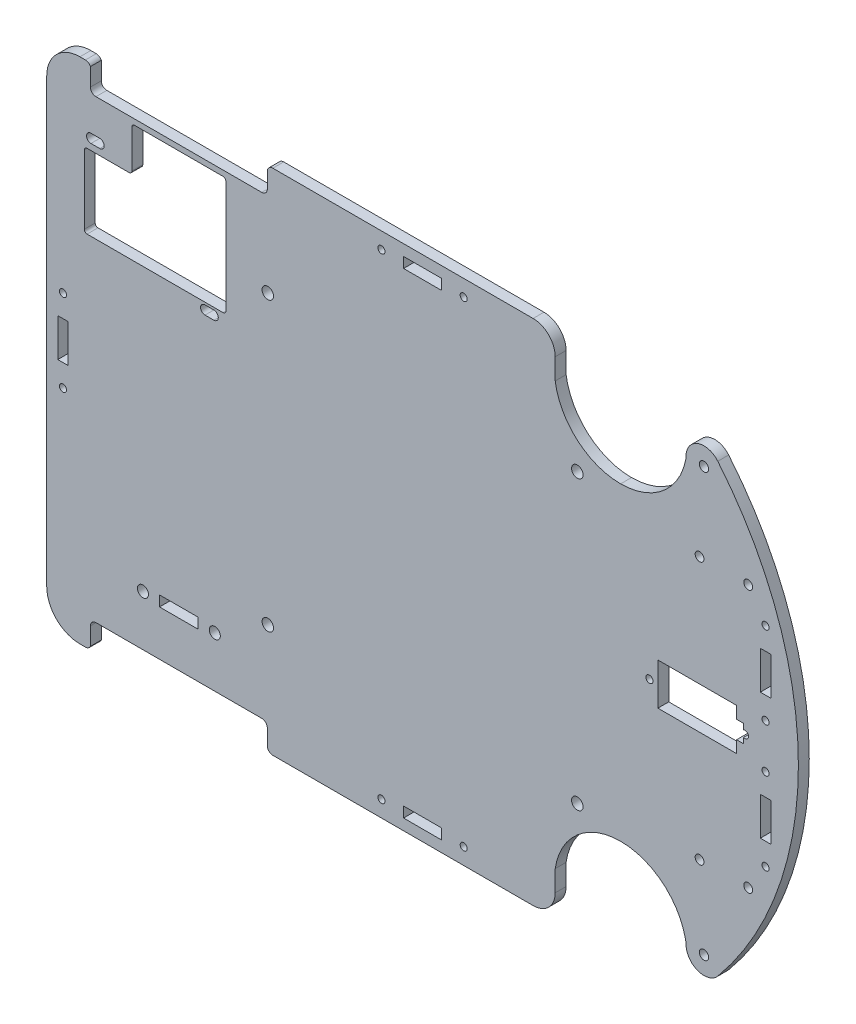
SolidWorks part; units mm, degrees
ref_plane "Alzado" through (0, 0, 0) normal (0, 0, 1) x (1, 0, 0)
ref_plane "Planta" through (0, 0, 0) normal (0, 1, 0) x (1, 0, 0)
ref_plane "Vista lateral" through (0, 0, 0) normal (1, 0, 0) x (0, 0, -1)
sketch "Croquis1" plane through (0, 0, 0) normal (0, 0, 1) x (1, 0, 0)
  line L1 (-107.95, -73.025) -> (107.95, -73.025)
  line L2 (-107.95, -73.025) -> (-107.95, 73.025)
  line L3 (-107.95, 73.025) -> (107.95, 73.025)
  line L4 (107.95, -73.025) -> (107.95, 73.025)
  line L5 (-107.95, -73.025) -> (107.95, 73.025) construction
  line L6 (-107.95, 73.025) -> (107.95, -73.025) construction
  point P0 (0, 0)
  dimension "D1" = 146.05
  dimension "D2" = 215.9
extrude "Saliente-Extruir1" add sketch "Croquis1" along normal blind 3.1242
sketch "Croquis2" plane through (0, 0, 3.1242) normal (0, 0, 1) x (1, 0, 0)
  line L0 (-107.95, -73.025) -> (107.95, -73.025) construction
  line L1 (107.95, 73.025) -> (43.634, 73.025)
  line L2 (107.95, 73.025) -> (107.95, -73.025)
  line L3 (107.95, -73.025) -> (43.634, -73.025)
  line L4 (43.634, 73.025) -> (43.634, -73.025)
  line L5 (0, 0) -> (107.95, 0) construction
  line L6 (71.3851, 73.025) -> (80.1989, 73.025)
  line L7 (71.3851, 73.025) -> (71.3851, 55.6514)
  line L8 (71.3851, 55.6514) -> (80.1989, 55.6514)
  line L9 (80.1989, 73.025) -> (80.1989, 55.6514)
  line L10 (80.1989, -73.025) -> (80.1989, -55.6514)
  line L11 (71.3851, -55.6514) -> (80.1989, -55.6514)
  line L12 (71.3851, -73.025) -> (71.3851, -55.6514)
  line L13 (71.3851, -73.025) -> (80.1989, -73.025)
  circle A0 centre (80.8339, 60.7314) radius 2.921
  circle A1 centre (80.8339, 60.7314) radius 1.3335
  circle A2 centre (80.8339, -60.7314) radius 1.3335
  circle A3 centre (80.8339, -60.7314) radius 2.921
  point P11 (75.792, 73.025)
  point P12 (75.792, 55.6514)
  point P13 (80.8339, 57.8104)
  point P14 (83.7549, 60.7314)
  point P28 (83.7549, -60.7314)
  point P29 (80.8339, -57.8104)
  point P30 (75.792, -55.6514)
  point P31 (75.792, -73.025)
  point P32 (80.8339, -59.3979)
  point P33 (80.8339, 59.3979)
  point P34 (80.8339, -62.0649)
  point P35 (80.8339, 62.0649)
  dimension "D3" = 5.842
  dimension "D4" = 1.5875
  dimension "D1" = 43.634
  dimension "D2" = 8.8138
  dimension "D5" = 3.556
  dimension "D6" = 17.3736
  dimension "D7" = 118.7958
  dimension "D8" = 118.7958
  dimension "D9" = 124.1298
extrude "Cortar-Extruir1" cut sketch "Croquis2" against normal through all contours L9 A1 | L9 A1 | A2 region at (81.0771, 60.7314, 3.1242) region at (79.9121, 60.7314, 3.1242)
sketch "Croquis9" plane through (0, 0, 3.1242) normal (0, 0, 1) x (1, 0, 0)
  line L0 (68.1339, 37.6809) -> (93.5339, 37.6809) construction
  line L1 (0, 0) -> (107.95, 0) construction
  line L2 (107.95, -73.025) -> (107.95, 73.025) construction
  line L3 (68.1339, -37.6809) -> (93.5339, -37.6809) construction
  circle A0 centre (68.1339, 37.6809) radius 1.27
  circle A1 centre (93.5339, 37.6809) radius 1.27
  circle A2 centre (93.5339, 37.6809) radius 2.794
  circle A3 centre (80.8339, 60.7314) radius 1.3335 construction
  circle A4 centre (80.8339, 60.7314) radius 1.3335
  circle A5 centre (93.5339, -37.6809) radius 1.27
  circle A6 centre (68.1339, -37.6809) radius 1.27
  circle A7 centre (80.8339, 37.6809) radius 1.27
  circle A8 centre (80.8339, -37.6809) radius 1.27
  circle A9 centre (79.5639, 37.6809) radius 1.27
  circle A10 centre (79.5639, -37.6809) radius 1.27
  point P4 (80.8339, 62.0649)
  point P5 (93.5339, 34.8869)
  point P9 (80.8339, 37.6809)
  point P22 (93.5339, -34.8869)
  point P23 (69.4039, 37.6809)
  point P24 (92.2639, 37.6809)
  dimension "D1" = 12.7
  dimension "D2" = 2.54
  dimension "D3" = 27.178
  dimension "D4" = 5.588
  dimension "D5" = 23.0505
  dimension "D6" = 2.667
extrude "Cortar-Extruir6" cut sketch "Croquis9" against normal through all contours A9 | A1 | A10 | A5
sketch "Croquis3" plane through (0, 0, 3.1242) normal (0, 0, 1) x (1, 0, 0)
  line L0 (107.95, -73.025) -> (107.95, 73.025) construction
  line L1 (107.95, 73.025) -> (-107.95, 73.025) construction
  line L2 (0, 0) -> (107.95, 0) construction
  line L3 (38.1, 73.025) -> (75.6745, 73.025)
  line L4 (38.1, 73.025) -> (38.1, 44.45)
  line L5 (38.1, 44.45) -> (75.6745, 44.45)
  line L6 (75.6745, 73.025) -> (75.6745, 44.45)
  line L7 (75.6745, -73.025) -> (75.6745, -44.45)
  line L8 (38.1, -44.45) -> (75.6745, -44.45)
  line L9 (38.1, -73.025) -> (38.1, -44.45)
  line L10 (38.1, -73.025) -> (75.6745, -73.025)
  line L11 (-107.95, -73.025) -> (107.95, -73.025) construction
  line L12 (-98.425, 73.025) -> (0, 73.025)
  line L13 (-107.95, 63.5) -> (-107.95, -63.5)
  line L14 (-98.425, -73.025) -> (0, -73.025)
  line L15 (0, 73.025) -> (0, -73.025)
  circle A0 centre (80.8339, 60.7314) radius 5.1594
  arc A1 (84.8004, 64.0308) -> (84.8004, -64.0308) centre (7.8219, 0) cw
  arc A2 (75.6745, 60.7314) -> (75.5727, 59.7195) centre (70.5945, 60.7314) cw
  arc A3 (31.75, 73.025) -> (38.1, 66.675) centre (31.75, 66.675) cw
  arc A4 (38.0482, 65.8655) -> (56.8873, 44.45) centre (56.8873, 63.4441) ccw
  arc A5 (38.0482, -65.8655) -> (56.8873, -44.45) centre (56.8873, -63.4441) cw
  arc A6 (31.75, -73.025) -> (38.1, -66.675) centre (31.75, -66.675) ccw
  arc A7 (75.5727, -59.7195) -> (56.8873, -44.45) centre (56.8873, -63.5176) ccw
  circle A8 centre (80.8339, -60.7314) radius 5.1594
  arc A9 (-107.95, -63.5) -> (-98.425, -73.025) centre (-98.425, -63.5) ccw
  arc A10 (-98.425, 73.025) -> (-107.95, 63.5) centre (-98.425, 63.5) ccw
  arc A11 (75.5727, 59.7195) -> (56.8873, 44.45) centre (56.8873, 63.5176) cw
  arc A12 (75.6745, -60.7314) -> (75.5727, -59.7195) centre (70.5945, -60.7314) ccw
  point P48 (-107.95, 73.025)
  line M6 (107.95, -73.025) -> (107.95, 73.025)
  line M7 (107.95, 73.025) -> (-107.95, 73.025)
  line M8 (-107.95, 73.025) -> (-107.95, -73.025)
  line M9 (-107.95, -73.025) -> (107.95, -73.025)
  dimension "D1" = 28.575
  dimension "D3" = 6.35
  dimension "D4" = 9.525
  dimension "D5" = 10.3187
  dimension "D6" = 5.08
  dimension "D2" = 38.1
extrude "Cortar-Extruir2" cut sketch "Croquis3" against normal through all contours A3 A4 L4 M7 | A11 A2 L6 L4 A4 M7 | A0 A1 L6 M6 M7 | A1 A8 L7 M9 M6 | L7 A12 A7 A5 L9 M9 | A6 L9 A5 M9 | A10 M7 M8 | A9 M8 M9 region at (56.8973, 60.3698, 3.1242) region at (36.6816, 71.6066, 3.1242) region at (97.7834, 56.0016, 3.1242) region at (97.7834, -56.0016, 3.1242) region at (-105.8224, 70.8974, 3.1242) region at (-105.8224, -70.8974, 3.1242) region at (36.6816, -71.6066, 3.1242) region at (56.8973, -60.3698, 3.1242)
sketch "Croquis5" plane through (0, 0, 3.1242) normal (0, 0, 1) x (1, 0, 0)
  line L0 (-98.425, -73.025) -> (31.75, -73.025) construction
  line L1 (-17.0815, -19.2786) -> (33.3375, -19.2786)
  line L2 (-17.0815, -19.2786) -> (-17.0815, -69.85)
  line L3 (-17.0815, -69.85) -> (33.3375, -69.85)
  line L4 (33.3375, -19.2786) -> (33.3375, -69.85)
  line L5 (-17.0815, -44.5643) -> (33.3375, -44.5643) construction
  line L6 (38.1, -66.675) -> (38.1, -60.6489) construction
  line L7 (33.3375, -69.85) -> (25.9715, -69.85)
  line L8 (33.3375, -69.85) -> (33.3375, -19.2786)
  line L9 (33.3375, -19.2786) -> (25.9715, -19.2786)
  line L10 (25.9715, -69.85) -> (25.9715, -19.2786)
  line L11 (-17.0815, -19.2786) -> (-6.9215, -19.2786)
  line L12 (-17.0815, -19.2786) -> (-17.0815, -69.85)
  line L13 (-17.0815, -69.85) -> (-6.9215, -69.85)
  line L14 (-6.9215, -19.2786) -> (-6.9215, -69.85)
  line L15 (25.9715, -33.2486) -> (33.3375, -33.2486)
  line L16 (25.9715, -33.2486) -> (25.9715, -55.88)
  line L17 (25.9715, -55.88) -> (33.3375, -55.88)
  line L18 (33.3375, -33.2486) -> (33.3375, -55.88)
  line L19 (-6.9215, -29.0576) -> (-17.0815, -29.0576)
  line L20 (-6.9215, -29.0576) -> (-6.9215, -60.071)
  line L21 (-6.9215, -60.071) -> (-17.0815, -60.071)
  line L22 (-17.0815, -29.0576) -> (-17.0815, -60.071)
  circle A0 centre (29.7815, -24.7396) radius 1.651
  circle A1 centre (-10.3505, -24.6126) radius 1.651
  circle A2 centre (29.7815, -64.389) radius 1.651
  circle A3 centre (-10.3505, -64.516) radius 1.651
  arc A4 (31.75, -55.88) -> (33.3375, -54.2925) centre (31.75, -54.2925) ccw
  arc A5 (29.6545, -55.88) -> (25.9715, -59.563) centre (29.6545, -59.563) ccw
  arc A6 (-12.0015, -60.071) -> (-17.0815, -54.991) centre (-12.0015, -54.991) cw
  arc A7 (-10.0965, -60.071) -> (-6.9215, -63.246) centre (-10.0965, -63.246) cw
  arc A8 (31.75, -33.2486) -> (33.3375, -34.8361) centre (31.75, -34.8361) cw
  arc A9 (29.6545, -33.2486) -> (25.9715, -29.5656) centre (29.6545, -29.5656) cw
  arc A10 (-12.0015, -29.0576) -> (-17.0815, -34.1376) centre (-12.0015, -34.1376) ccw
  arc A11 (-10.0965, -29.0576) -> (-6.9215, -25.8826) centre (-10.0965, -25.8826) ccw
  arc A12 (-6.9215, -20.0724) -> (-6.1278, -19.2786) centre (-6.1278, -20.0724) cw
  arc A13 (25.1777, -19.2786) -> (25.9715, -20.0724) centre (25.1777, -20.0724) cw
  arc A14 (25.1777, -69.85) -> (25.9715, -69.0563) centre (25.1777, -69.0563) ccw
  arc A15 (-6.9215, -69.0563) -> (-6.1278, -69.85) centre (-6.1278, -69.0563) ccw
  point P4 (31.4325, -24.7396)
  point P5 (29.7815, -23.0886)
  point P6 (-10.3505, -22.9616)
  point P14 (-12.0015, -24.6126)
  dimension "D5" = 3.302
  dimension "D16" = 1.5875
  dimension "D17" = 3.175
  dimension "D18" = 0.7937
  dimension "D1" = 50.5714
  dimension "D2" = 50.419
  dimension "D3" = 3.81
  dimension "D4" = 1.905
  dimension "D6" = 3.175
  dimension "D7" = 4.7625
  dimension "D8" = 5.08
  dimension "D9" = 3.683
  dimension "D10" = 7.366
  dimension "D11" = 10.16
  dimension "D12" = 13.97
  dimension "D13" = 13.97
  dimension "D14" = 9.779
  dimension "D15" = 9.779
extrude "Driver" [suppressed] cut sketch "Croquis5" against normal through all contours L22 L5 L14 L19 A10 | L5 L12 A6 L21 L20 | L14 L5 L16 L10 L1 | L16 L5 L18 A8 L15 | L5 L10 L17 A4 L8 | L5 L20 L14 L3 L10 | A5 L17 L10 | L21 A7 L14 | A11 L19 L14 | L15 A9 L10 | A1 | A3 | A2 | A0
sketch "Croquis6" [suppressed] plane through (0, 0, 3.1242) normal (0, 0, 1) x (1, 0, 0)
  line L0 (-33.45, 19.8814) -> (22.55, 19.8814)
  line L1 (-29.95, 48.8814) -> (19.05, 48.8814)
  line L2 (-29.95, 48.8814) -> (-29.95, -9.1186)
  line L3 (-29.95, -9.1186) -> (19.05, -9.1186)
  line L4 (19.05, 48.8814) -> (19.05, -9.1186)
  line L5 (-6.1278, -19.2786) -> (25.1777, -19.2786) construction
  line L6 (-5.45, -9.1186) -> (-5.45, 74.7014)
  line L7 (38.1, 66.675) -> (38.1, 60.6489) construction
  circle A0 centre (-29.95, 48.8814) radius 1.651
  circle A1 centre (19.05, 48.8814) radius 1.651
  circle A2 centre (19.05, -9.1186) radius 1.651
  circle A3 centre (-29.95, -9.1186) radius 1.651
  point P13 (-5.45, 19.8814)
  point P14 (19.05, 19.8814)
  point P16 (-5.45, 48.8814)
  point P19 (38.1, 63.662)
  dimension "D1" = 3.302
  dimension "D2" = 58
  dimension "D3" = 49
  dimension "D4" = 56
  dimension "D5" = 19.05
  dimension "D6" = 10.16
  dimension "D7" = 83.82
extrude "RasPi" [suppressed] cut sketch "Croquis6" against normal through all contours A3 | A2 | A1 | A0
sketch "Croquis8" plane through (0, 0, 3.1242) normal (0, 0, 1) x (1, 0, 0)
  line L0 (-93.98, 54.3306) -> (-61.214, 28.0162)
  line L1 (-62.484, 28.0162) -> (-59.944, 28.0162) construction
  line L7 (-62.484, 29.2862) -> (-59.944, 29.2862)
  line L11 (-62.484, 26.7462) -> (-59.944, 26.7462)
  line L13 (-77.597, 66.3702) -> (-77.597, -66.3702) construction
  line L14 (-95.25, 54.3306) -> (-92.71, 54.3306) construction
  line L15 (-95.25, 55.6006) -> (-92.71, 55.6006)
  line L16 (-95.25, 53.0606) -> (-92.71, 53.0606)
  circle A0 centre (-93.98, 54.3306) radius 1.27
  circle A1 centre (-61.214, 28.0162) radius 1.27
  arc A2 (-62.484, 29.2862) -> (-62.484, 26.7462) centre (-62.484, 28.0162) ccw
  arc A3 (-59.944, 26.7462) -> (-59.944, 29.2862) centre (-59.944, 28.0162) ccw
  arc A4 (-95.25, 55.6006) -> (-95.25, 53.0606) centre (-95.25, 54.3306) ccw
  arc A5 (-92.71, 53.0606) -> (-92.71, 55.6006) centre (-92.71, 54.3306) ccw
  point P8 (-61.214, 26.7462)
  point P9 (-93.98, 53.0606)
  point P10 (-95.25, 54.3306)
  point P12 (-59.944, 28.0162)
  point P14 (-77.597, 0)
  point P16 (-61.214, 28.0162)
  point P22 (-93.98, 54.3306)
  point P30 (-77.597, 41.1734)
  dimension "D1" = 13.3096
  dimension "D3" = 2.54
  dimension "D4" = 2.54
  dimension "D2" = 32.766
  dimension "D5" = 77.597
  dimension "D6" = 39.624
  dimension "D7" = 132.7404
extrude "Diferencial trasero" cut sketch "Croquis8" against normal through all contours A5 L15 A4 L16 | A3 L7 A2 L11
sketch "Croquis11" plane through (0, 0, 3.1242) normal (0, 0, 1) x (1, 0, 0)
  line L0 (-98.425, 73.025) -> (-95.25, 73.025)
  line L1 (-82.6984, 63.8302) -> (-57.2984, 63.8302)
  line L2 (-83.4921, 63.0365) -> (-83.4921, 29.9529)
  line L3 (-83.4921, 29.9529) -> (-57.2984, 29.9529)
  line L4 (-56.5046, 63.0365) -> (-56.5046, 30.7467)
  line L5 (-56.5046, 29.9529) -> (-96.3613, 29.953)
  line L6 (-56.5046, 29.9529) -> (-56.5046, 51.2889)
  line L7 (-56.5046, 51.2889) -> (-96.3613, 51.2889)
  line L8 (-97.155, 30.7467) -> (-97.155, 50.4952)
  line L9 (-107.95, 63.5) -> (-107.95, -63.5) construction
  line L10 (31.75, 73.025) -> (-98.425, 73.025) construction
  line L11 (-95.25, 73.025) -> (-53.3296, 73.025)
  line L12 (-95.25, 73.025) -> (-95.25, 65.4177)
  line L13 (-95.25, 65.4177) -> (-53.3296, 65.4177)
  line L14 (-53.3296, 73.025) -> (-53.3296, 65.4177)
  line L15 (-43.0109, 73.025) -> (-44.5984, 73.025)
  line L16 (-95.3984, 80.6323) -> (-44.5984, 80.6323)
  line L17 (-95.3984, 80.6323) -> (-95.3984, 67.0052)
  line L18 (-93.8109, 65.4177) -> (-46.1859, 65.4177)
  line L19 (-44.5984, 80.6323) -> (-44.5984, 67.0052)
  line L20 (-95.3984, 80.6323) -> (-44.5984, 65.4177) construction
  line L21 (-95.3984, 65.4177) -> (-44.5984, 80.6323) construction
  line L22 (0, 0) -> (-107.95, 0) construction
  line L23 (-95.3984, -65.4177) -> (-44.5984, -80.6323) construction
  line L24 (-95.3984, -80.6323) -> (-44.5984, -65.4177) construction
  line L25 (-44.5984, -80.6323) -> (-44.5984, -67.0052)
  line L26 (-93.8109, -65.4177) -> (-46.1859, -65.4177)
  line L27 (-95.3984, -80.6323) -> (-95.3984, -67.0052)
  line L28 (-95.3984, -80.6323) -> (-44.5984, -80.6323)
  line L29 (-43.0109, -73.025) -> (-44.5984, -73.025)
  line L30 (-53.3296, -73.025) -> (-53.3296, -65.4177)
  line L31 (-95.25, -65.4177) -> (-53.3296, -65.4177)
  line L32 (-95.25, -73.025) -> (-95.25, -65.4177)
  line L33 (-95.25, -73.025) -> (-53.3296, -73.025)
  line L34 (-95.25, -73.025) -> (-95.25, -65.4177)
  line L35 (-98.425, -73.025) -> (-95.25, -73.025)
  circle A0 centre (-61.214, 28.0162) radius 1.27 construction
  arc A1 (-96.3613, 29.953) -> (-97.155, 30.7467) centre (-96.3613, 30.7467) cw
  arc A2 (-96.3613, 51.2889) -> (-97.155, 50.4952) centre (-96.3613, 50.4952) ccw
  arc A3 (-57.2984, 29.9529) -> (-56.5046, 30.7467) centre (-57.2984, 30.7467) ccw
  arc A4 (-57.2984, 63.8302) -> (-56.5046, 63.0365) centre (-57.2984, 63.0365) cw
  arc A5 (-82.6984, 63.8302) -> (-83.4921, 63.0365) centre (-82.6984, 63.0365) ccw
  arc A6 (-83.4921, 52.0827) -> (-84.2859, 51.2889) centre (-84.2859, 52.0827) cw
  circle A7 centre (-93.98, 54.3306) radius 1.27 construction
  circle A8 centre (-93.98, 54.3306) radius 1.27
  arc A9 (-46.1859, 65.4177) -> (-44.5984, 67.0052) centre (-46.1859, 67.0052) ccw
  arc A10 (-95.3984, 67.0052) -> (-93.8109, 65.4177) centre (-93.8109, 67.0052) ccw
  arc A11 (-44.5984, 71.4375) -> (-43.0109, 73.025) centre (-43.0109, 71.4375) cw
  arc A12 (-95.25, 71.4375) -> (-96.8375, 73.025) centre (-96.8375, 71.4375) ccw
  arc A13 (-107.95, -63.5) -> (-98.425, -73.025) centre (-98.425, -63.5) ccw
  arc A14 (-107.95, 63.5) -> (-98.425, 73.025) centre (-98.425, 63.5) cw
  arc A15 (-95.25, -71.4375) -> (-96.8375, -73.025) centre (-96.8375, -71.4375) cw
  arc A17 (-44.5984, -71.4375) -> (-43.0109, -73.025) centre (-43.0109, -71.4375) ccw
  arc A18 (-95.3984, -67.0052) -> (-93.8109, -65.4177) centre (-93.8109, -67.0052) cw
  arc A19 (-46.1859, -65.4177) -> (-44.5984, -67.0052) centre (-46.1859, -67.0052) cw
  point P11 (-59.993, 28.3654)
  point P16 (-97.155, 29.953)
  point P19 (-97.155, 51.2889)
  point P37 (-95.25, 54.3306)
  point P38 (-69.9984, 73.025)
  point P46 (-69.9984, 63.8302)
  point P60 (0, 0)
  point P61 (-96.3613, 73.025)
  point P62 (0, 0)
  point P91 (-69.9984, -73.025)
  point P92 (-59.944, 29.2862)
  dimension "D8" = 0.7937
  dimension "D9" = 1.5875
  dimension "D4" = 3.0417
  dimension "D11" = 50.8
  dimension "D12" = 1.5875
  dimension "D13" = 1.5875
  dimension "D2" = 3.175
  dimension "D3" = 10.4879
  dimension "D5" = 21.336
  dimension "D6" = 26.9875
  dimension "D7" = 9.4996
  dimension "D10" = 3.175
extrude "Entrada transmision" cut sketch "Croquis11" against normal through all contours L1 A5 L2 L7 L4 A4 | L3 A3 L4 L7 L2 | L7 A2 L8 A1 L5 L2 | L2 A6 L7 | L17 A10 L18 L12 L11 L14 A9 L19 L16 | L14 L11 L12 L13 | L19 A11 L15 | L12 L17 A10 L18 | L17 | L27 | A18 L27 L32 L26 | L32 L33 L30 L26 | A19 L26 L30 L33 L27 L28 L25 | A17 L25 L29 | L32 A15 L27 L35 | A12 L12 L0 L17 region at (-95.7343, 72.7721, 3.1242) region at (-66.9396, 75.7248, 3.1242) region at (-95.3184, 72.4459, 3.1242) region at (-95.3242, 69.2214, 3.1242) region at (-74.2657, 69.2255, 3.1242) region at (-44.2438, 72.6704, 3.1242) region at (-69.9984, 57.5547, 3.1242) region at (-83.6694, 51.4662, 3.1242) region at (-70.0015, 40.6234, 3.1242) region at (-90.3174, 40.6209, 3.1242) region at (-66.9396, -75.7248, 3.1242) region at (-44.2438, -72.6704, 3.1242) region at (-95.7343, -72.7721, 3.1242) region at (-95.3184, -72.4459, 3.1242) region at (-95.3242, -69.2214, 3.1242) region at (-74.2657, -69.2255, 3.1242)
sketch "Croquis10" plane through (0, 0, 3.1242) normal (0, 0, 1) x (1, 0, 0)
  line L0 (-107.95, 63.5) -> (-107.95, -63.5) construction
  line L1 (61.3912, -19.4466) -> (51.7144, -19.4466)
  line L2 (61.3912, -19.4466) -> (61.3912, 12.2487)
  line L3 (61.3912, 12.2487) -> (51.7144, 12.2487)
  line L4 (51.7144, -19.4466) -> (51.7144, 12.2487)
  line L5 (61.3912, -19.4466) -> (51.7144, 12.2487) construction
  line L6 (61.3912, 12.2487) -> (51.7144, -19.4466) construction
  line L8 (67.5894, -5.9944) -> (90.1954, -5.9944)
  line L9 (67.5894, -5.9944) -> (67.5894, 5.9944)
  line L10 (67.5894, 5.9944) -> (90.1954, 5.9944)
  line L11 (90.1954, -5.9944) -> (90.1954, 5.9944)
  line L12 (67.5894, -5.9944) -> (90.1954, 5.9944) construction
  line L13 (67.5894, 5.9944) -> (90.1954, -5.9944) construction
  line L14 (90.1954, -5.9944) -> (90.1954, 5.9944)
  line L15 (90.1954, 3.1134) -> (90.1954, -1.9666)
  line L18 (90.1954, -2.54) -> (92.2274, -2.54)
  line L19 (90.1954, -2.54) -> (90.1954, 2.54)
  line L20 (90.1954, 2.54) -> (92.2274, 2.54)
  line L21 (92.2274, -2.54) -> (92.2274, 2.54)
  circle A3 centre (65.1637, 0) radius 1.016
  circle A4 centre (92.6211, 0) radius 1.016
  point P0 (56.5528, -3.599)
  point P16 (78.8924, 0)
  point P21 (90.1954, 0)
  point P26 (92.2274, 0)
  point P31 (0, 0)
  point P32 (0, 0)
  dimension "D5" = 2.4257
  dimension "D2" = 2.032
  dimension "D1" = 159.6644
  dimension "D3" = 22.606
  dimension "D4" = 11.9888
  dimension "D6" = 2.4257
  dimension "D7" = 175.5394
  dimension "D8" = 2.032
  dimension "D9" = 5.08
extrude "Servo" cut sketch "Croquis10" against normal through all contours L8 L11 L14 L10 L9 | L18 L21 L20 L14 | A4 | A3 region at (78.8924, 0, 3.1242) region at (91.144, 0, 3.1242)
sketch "Croquis12" plane through (0, 0, 3.1242) normal (0, 0, 1) x (1, 0, 0)
  line L1 (-44.45, -41.275) -> (44.45, -41.275)
  line L2 (-44.45, -41.275) -> (-44.45, 41.275)
  line L3 (-44.45, 41.275) -> (44.45, 41.275)
  line L4 (44.45, -41.275) -> (44.45, 41.275)
  line L5 (-44.45, -41.275) -> (44.45, 41.275) construction
  line L6 (-44.45, 41.275) -> (44.45, -41.275) construction
  circle A2 centre (44.45, 41.275) radius 1.651
  circle A3 centre (-44.45, 41.275) radius 1.651
  circle A4 centre (-44.45, -41.275) radius 1.651
  circle A5 centre (44.45, -41.275) radius 1.651
  point P0 (0, 0)
  dimension "D1" = 3.302
  dimension "D2" = 88.9
  dimension "D3" = 82.55
extrude "Soportes BS" cut sketch "Croquis12" against normal through all contours A3 | A2 | A5 | A4
sketch "Croquis7" plane through (0, 0, 3.1242) normal (0, 0, 1) x (1, 0, 0)
  line L0 (-93.8109, -65.4177) -> (-46.1859, -65.4177) construction
  line L1 (-75.5546, -49.3903) -> (-64.4421, -49.3903)
  line L2 (-75.5546, -49.3903) -> (-75.5546, -52.3875)
  line L3 (-75.5546, -52.3875) -> (-64.4421, -52.3875)
  line L4 (-64.4421, -49.3903) -> (-64.4421, -52.3875)
  line L9 (-98.425, -73.025) -> (-96.8375, -73.025) construction
  circle A0 centre (-59.6796, -50.8889) radius 1.5875
  circle A1 centre (-80.3171, -50.8889) radius 1.5875
  point P6 (-69.9984, -52.3875)
  point P7 (-69.9984, -65.4177)
  point P8 (0, 0)
  point P9 (0, 0)
  point P16 (-64.4421, -50.8889)
  point P17 (0, 0)
  dimension "D4" = 3.175
  dimension "D1" = 2.9972
  dimension "D2" = 11.1125
  dimension "D3" = 20.6375
  dimension "D5" = 4.7625
  dimension "D6" = 4.7625
extrude "Soporte eje" cut sketch "Croquis7" against normal through all contours A1 | A0 | L3 L4 L1 L2 region at (-59.6796, -50.8889, 3.1242) region at (-80.3171, -50.8889, 3.1242)
sketch "Croquis13" plane through (0, 0, 3.1242) normal (0, 0, 1) x (1, 0, 0)
  line L0 (0, 0) -> (107.95, 0) construction
  line L1 (0, -73.025) -> (0, 73.025) construction
  line L2 (101.7778, -5.461) -> (104.775, -5.461)
  line L3 (101.7778, -5.461) -> (101.7778, 5.461)
  line L4 (101.7778, 5.461) -> (104.775, 5.461)
  line L5 (104.775, -5.461) -> (104.775, 5.461)
  line L6 (101.7778, -5.461) -> (104.775, 5.461) construction
  line L7 (101.7778, 5.461) -> (104.775, -5.461) construction
  line L8 (31.75, 73.025) -> (-43.0109, 73.025) construction
  line L9 (-101.7778, 5.461) -> (-104.775, -5.461) construction
  line L10 (-5.461, 66.8528) -> (5.461, 66.8528)
  line L11 (-5.461, 66.8528) -> (-5.461, 69.85)
  line L12 (-5.461, 69.85) -> (5.461, 69.85)
  line L13 (5.461, 66.8528) -> (5.461, 69.85)
  line L14 (-5.461, 66.8528) -> (5.461, 69.85) construction
  line L15 (-5.461, 69.85) -> (5.461, 66.8528) construction
  line L16 (-101.7778, -5.461) -> (-104.775, 5.461) construction
  line L17 (-104.775, -5.461) -> (-104.775, 5.461)
  line L18 (-101.7778, 5.461) -> (-104.775, 5.461)
  line L19 (-101.7778, -5.461) -> (-101.7778, 5.461)
  line L20 (-101.7778, -5.461) -> (-104.775, -5.461)
  line L21 (-5.461, -69.85) -> (5.461, -66.8528) construction
  line L22 (-5.461, -66.8528) -> (5.461, -69.85) construction
  line L23 (5.461, -66.8528) -> (5.461, -69.85)
  line L24 (-5.461, -69.85) -> (5.461, -69.85)
  line L25 (-5.461, -66.8528) -> (-5.461, -69.85)
  line L26 (-5.461, -66.8528) -> (5.461, -66.8528)
  line L27 (97.0153, 12.7) -> (100.0125, 23.622) construction
  line L28 (100.0125, 12.7) -> (100.0125, 23.622)
  line L29 (97.0153, 12.7) -> (97.0153, 23.622)
  line L30 (97.0153, 23.622) -> (100.0125, 23.622)
  line L31 (97.0153, 23.622) -> (100.0125, 12.7) construction
  line L32 (97.0153, 12.7) -> (100.0125, 12.7)
  line L33 (97.0153, -23.622) -> (100.0125, -12.7) construction
  line L34 (97.0153, -12.7) -> (100.0125, -23.622) construction
  line L35 (97.0153, -12.7) -> (100.0125, -12.7)
  line L36 (97.0153, -23.622) -> (100.0125, -23.622)
  line L37 (97.0153, -12.7) -> (97.0153, -23.622)
  line L38 (100.0125, -12.7) -> (100.0125, -23.622)
  arc A0 (84.8004, -64.0308) -> (84.8004, 64.0308) centre (7.8219, 0) ccw construction
  circle A1 centre (103.2764, 11.811) radius 1.016
  circle A3 centre (103.2764, -11.811) radius 1.016
  circle A4 centre (11.811, 68.3514) radius 1.016
  circle A5 centre (-103.2764, 11.811) radius 1.016
  circle A6 centre (-103.2764, -11.811) radius 1.016
  circle A7 centre (-11.811, 68.3514) radius 1.016
  circle A8 centre (-11.811, -68.3514) radius 1.016
  circle A9 centre (11.811, -68.3514) radius 1.016
  circle A10 centre (98.5139, 29.972) radius 1.016
  circle A11 centre (98.5139, 6.35) radius 1.016
  circle A12 centre (98.5139, -6.35) radius 1.016
  circle A13 centre (98.5139, -29.972) radius 1.016
  point P6 (103.2764, 0)
  point P15 (0, 68.3514)
  point P25 (98.5139, 18.161)
  point P34 (-103.2764, 0)
  point P46 (0, -68.3514)
  point P55 (99.1418, 16.197)
  point P56 (98.6028, 18.161)
  point P57 (0, 0)
  point P58 (0, 0)
  point P59 (0, 0)
  point P68 (98.5139, -18.161)
  dimension "D4" = 6.35
  dimension "D5" = 2.032
  dimension "D6" = 3.175
  dimension "D8" = 6.35
  dimension "D1" = 2.9972
  dimension "D2" = 10.922
  dimension "D3" = 3.175
  dimension "D7" = 6.35
  dimension "D9" = 6.35
  dimension "D10" = 6.35
  dimension "D11" = 12.7
  dimension "D12" = 7.9375
extrude "Sensores de presencia" cut sketch "Croquis13" against normal through all contours L32 L28 L30 L29 | L35 L38 L36 L37 | A12 | A13 | A10 | A11 | A4 | L10 L13 L12 L11 | A7 | A9 | L24 L23 L26 L25 | A8 | A5 | L18 L17 L20 L19 | A6
